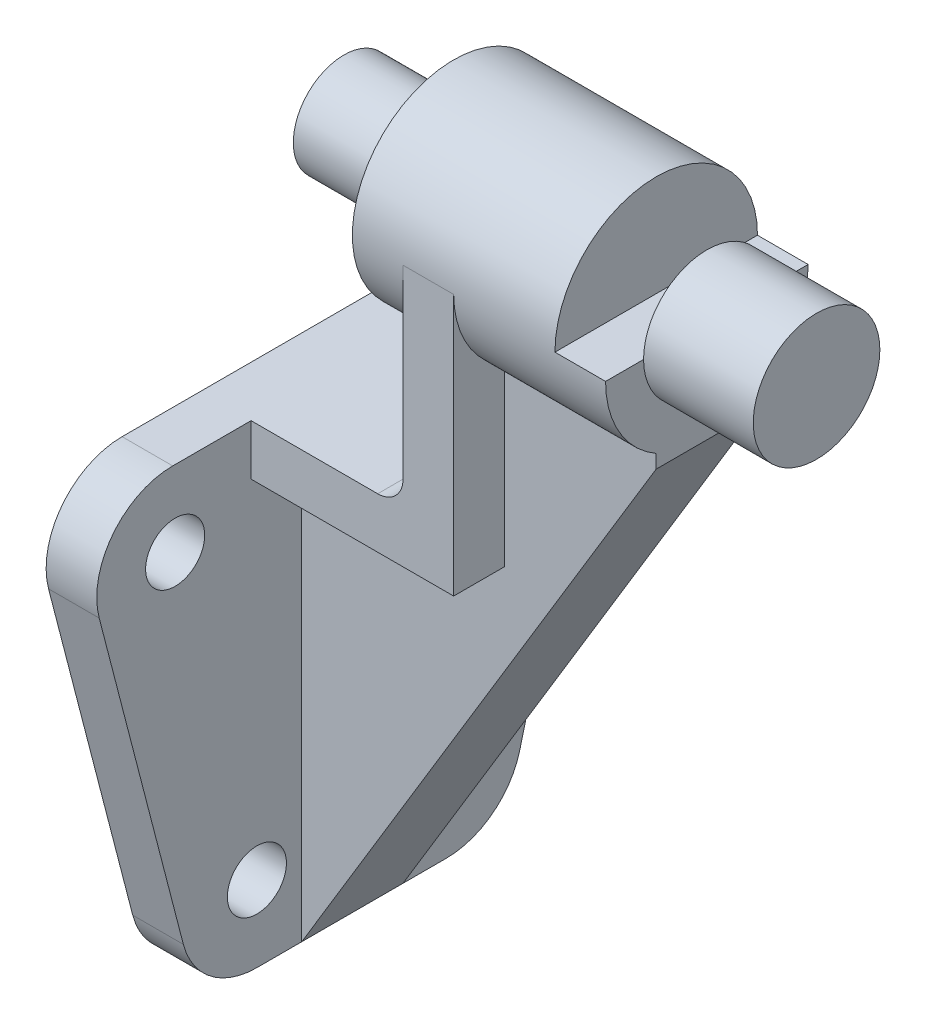
SolidWorks part; units mm, degrees
ref_plane "Front Plane" through (0, 0, 0) normal (0, 0, 1) x (1, 0, 0)
ref_plane "Top Plane" through (0, 0, 0) normal (0, 1, 0) x (1, 0, 0)
ref_plane "Right Plane" through (0, 0, 0) normal (1, 0, 0) x (0, 0, -1)
sketch "Sketch1" plane through (0, 0, 0) normal (1, 0, 0) x (0, 0, -1)
  line L0 (-59.9956, 5.5056) -> (-40.0509, -71.4386)
  line L1 (-22.6268, -84.9221) -> (22.2461, -84.9221)
  line L2 (39.6876, -71.3713) -> (59.3157, 5.5729)
  line L3 (41.8742, 28.0221) -> (-42.5715, 28.0221)
  line L4 (0, 0) -> (0, -104.5814) construction
  circle A0 centre (-42, 10.0221) radius 7
  arc A2 (-59.9956, 5.5056) -> (-42.5715, 28.0221) centre (-42.5715, 10.0221) cw
  arc A3 (59.3157, 5.5729) -> (41.8742, 28.0221) centre (41.8742, 10.0221) ccw
  arc A4 (-22.6268, -84.9221) -> (-40.0509, -71.4386) centre (-22.6268, -66.9221) cw
  arc A5 (39.6876, -71.3713) -> (22.2461, -84.9221) centre (22.2461, -66.9221) cw
  circle A6 centre (-22.6268, -66.9221) radius 7
  circle A7 centre (42, 10.0221) radius 7
  circle A8 centre (22.6268, -66.9221) radius 7
  point P22 (0, 0)
  dimension "D6" = 18
  dimension "D7" = 18
  dimension "D8" = 18
  dimension "D9" = 18
  dimension "D2" = 44.8729
  dimension "D4" = 14
  dimension "D10" = 14
  dimension "D1" = 42
  dimension "D3" = 84
  dimension "D5" = 18
extrude "Boss-Extrude1" add sketch "Sketch1" along normal blind 12
ref_plane "Plane1" through (36, 0, 0) normal (1, 0, 0) x (0, 0, -1)
sketch "Sketch2" plane through (36, 0, 0) normal (1, 0, 0) x (0, 0, -1)
  line L0 (-22.6268, -84.9221) -> (22.2461, -84.9221) construction
  circle A0 centre (0, 78.0779) radius 24
  point P4 (0, 0)
  point P5 (0, 0)
  point P6 (18.8187, 57.7099)
  point P8 (0, 0)
  dimension "D1" = 48
  dimension "D2" = 163
extrude "Boss-Extrude2" add sketch "Sketch2" along normal blind 48 separate body
sketch "Sketch3" plane through (84, 0, 0) normal (1, 0, 0) x (0, 0, -1)
  line L0 (-24, 78.0779) -> (24, 78.0779)
  circle A0 centre (0, 78.0779) radius 24 construction
  arc A1 (-24, 78.0779) -> (24, 78.0779) centre (0, 78.0779) ccw
extrude "Boss-Extrude3" add sketch "Sketch3" along normal blind 12
sketch "Sketch4" plane through (96, 0, 0) normal (1, 0, 0) x (0, 0, -1)
  circle A0 centre (0, 78.0779) radius 15
  dimension "D1" = 30
extrude "Boss-Extrude4" add sketch "Sketch4" along normal blind 26
sketch "Sketch5" plane through (36, 0, 0) normal (-1, 0, 0) x (0, 0, 1)
  circle A0 centre (0, 78.0779) radius 12
  dimension "D1" = 24
  dimension "D2" = 24
extrude "Boss-Extrude5" add sketch "Sketch5" along normal blind 26
sketch "Sketch6" plane through (0, 0, 0) normal (0, 0, 1) x (1, 0, 0)
  line L0 (12, 28.0221) -> (48, 28.0221)
  line L2 (48, 28.0221) -> (48, 77.9292)
  line L3 (48, 77.9292) -> (60, 77.9292)
  line L4 (60, 77.9292) -> (60, 16.0221)
  line L5 (60, 16.0221) -> (12, 16.0221)
  line L6 (12, 5.5056) -> (12, 28.0221) construction
  line L7 (12, 28.0221) -> (12, 16.0221)
  line L8 (36, 78.0779) -> (84, 78.0779) construction
  line L9 (36, 90.0779) -> (36, 66.0779) construction
  dimension "D1" = 12
  dimension "D2" = 12
  dimension "D3" = 36
extrude "Boss-Extrude6" add sketch "Sketch6" along normal blind 24 and the other way blind 24
fillet "Fillet2" radius 6 1 edges at (48, 28.0221, 0)
sketch "Sketch8" plane through (0, 0, 0) normal (0, 0, 1) x (1, 0, 0)
  line L1 (12, 5.5056) -> (12, -71.4386) construction
  line L2 (12, 16.0221) -> (60, 16.0221) construction
  line L3 (60, 16.0221) -> (60, 77.9292) construction
  line L7 (12, 16.0221) -> (12, -84.9221)
  line L8 (12, 16.0221) -> (60, 16.0221)
  line L9 (60, 16.0221) -> (60, 54.0779)
  line L13 (12, 5.5056) -> (12, 28.0221) construction
  line L14 (12, 5.5056) -> (12, 16.0221)
  line L15 (54, 16.0221) -> (60, 16.0221)
  line L16 (60, 16.0221) -> (60, 22.0221)
  line L17 (12, -84.9221) -> (96, 54.0779)
  line L18 (96, 54.0779) -> (96, 78.0779)
  line L19 (96, 78.0779) -> (60, 77.9292)
  line L20 (60, 77.9292) -> (60, 54.0779)
extrude "Boss-Extrude8" add sketch "Sketch8" along normal blind 12 and the other way blind 12 contours L19 L20 L9 L8 L7 L17 L18 region at (48.22, 7.8131, 0)
